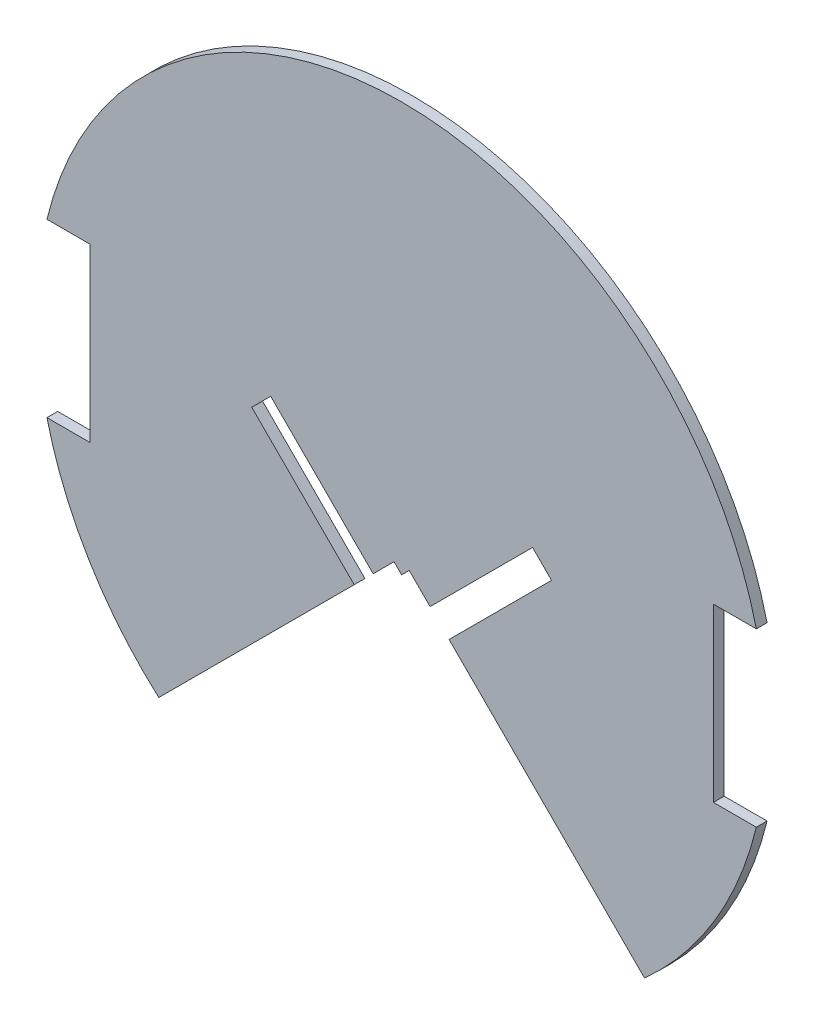
SolidWorks part; units mm, degrees
ref_plane "Front Plane" through (0, 0, 0) normal (0, 0, 1) x (1, 0, 0)
ref_plane "Top Plane" through (0, 0, 0) normal (0, 1, 0) x (1, 0, 0)
ref_plane "Right Plane" through (0, 0, 0) normal (1, 0, 0) x (0, 0, -1)
sketch "Sketch1" plane through (0, 0, 0) normal (0, 0, 1) x (1, 0, 0)
  circle A0 centre (0, 0) radius 215.9
  dimension "D1" = 431.8
extrude "Base Plate Extrusion" add sketch "Sketch1" along normal blind 6.35
sketch "Sketch2" plane through (0, 0, 6.35) normal (0, 0, 1) x (1, 0, 0)
  line L0 (0, 0) -> (0, -230.9791) construction
  line L1 (0, -17.4608) -> (143.6841, -161.1449)
  line L2 (0, -17.4608) -> (-143.6841, -161.1449)
  circle A1 centre (0, 0) radius 215.9 construction
  arc A2 (143.6841, -161.1449) -> (-143.6841, -161.1449) centre (0, 0) cw
  dimension "D1" = 90
  dimension "D2" = 203.2
extrude "V Funnel Cut" cut sketch "Sketch2" against normal through all
sketch "Sketch3" plane through (0, 0, 6.35) normal (0, 0, 1) x (1, 0, 0)
  line L0 (0, 0) -> (251.7982, 0) construction
  line L1 (209.8384, 50.8) -> (184.4384, 50.8)
  line L2 (209.8384, 50.8) -> (209.8384, -50.8)
  line L3 (209.8384, -50.8) -> (184.4384, -50.8)
  line L4 (184.4384, 50.8) -> (184.4384, -50.8)
  arc A0 (143.6841, -161.1449) -> (-143.6841, -161.1449) centre (0, 0) ccw construction
  arc A1 (209.8384, 50.8) -> (209.8384, -50.8) centre (0, 0) cw
  arc M7 (143.6841, -161.1449) -> (-143.6841, -161.1449) centre (0, 0) ccw
  dimension "D1" = 25.4
  dimension "D2" = 101.6
extrude "Wheel Track Cut" cut sketch "Sketch3" against normal through all contours L2 L0 A1 | L4 L0 L2 L1 | L0 L4 L3 L2 | L0 L2 M7 region at (197.1384, 25.4, 6.35) region at (197.1384, -25.4, 6.35) region at (212.266, 19.0862, 6.35) region at (212.266, -19.0862, 6.35)
mirror "Wheel Track Cut Mirror" about plane through (0, 0, 0) normal (1, 0, 0) of "Wheel Track Cut"
sketch "Sketch4" plane through (0, 0, 6.35) normal (0, 0, 1) x (1, 0, 0)
  line L0 (88.68, 15.0926) -> (77.4547, 26.3179)
  line L1 (88.68, 15.0926) -> (28.0633, -45.5241)
  line L2 (77.4547, 26.3179) -> (16.838, -34.2988)
  line L3 (28.0633, -45.5241) -> (16.838, -34.2988)
  line L4 (84.3174, 21.9553) -> (56.956, -5.4061) construction
  line L5 (65.1069, -1.7454) -> (69.5826, 2.7303) construction
  line L6 (65.0924, 7.2204) -> (60.6167, 2.7447) construction
  line L7 (143.6841, -161.1449) -> (0, -17.4608) construction
  dimension "D1" = 15.875
  dimension "D2" = 85.725
extrude "Cut-Extrude3" cut sketch "Sketch4" against normal through all
sketch "Sketch5" plane through (0, 0, 6.35) normal (0, 0, 1) x (1, 0, 0)
  line L0 (-4.4901, -21.951) -> (0, -17.4608)
  line L1 (-4.4901, -21.951) -> (0, -26.4411)
  line L2 (0, -17.4608) -> (4.4901, -21.951)
  line L3 (0, -26.4411) -> (4.4901, -21.951)
  line L4 (0, -17.4608) -> (-143.6841, -161.1449) construction
  line L6 (4.4901, -21.951) -> (0, -26.4411) construction
  dimension "D1" = 6.35
extrude "Boss-Extrude2" add sketch "Sketch5" against normal up to surface (6.35 mm away) up to face at (14.0691, -14.8765, 0)
mirror "Mirror2" about plane through (0, 0, 0) normal (1, 0, 0) of "Cut-Extrude3"
